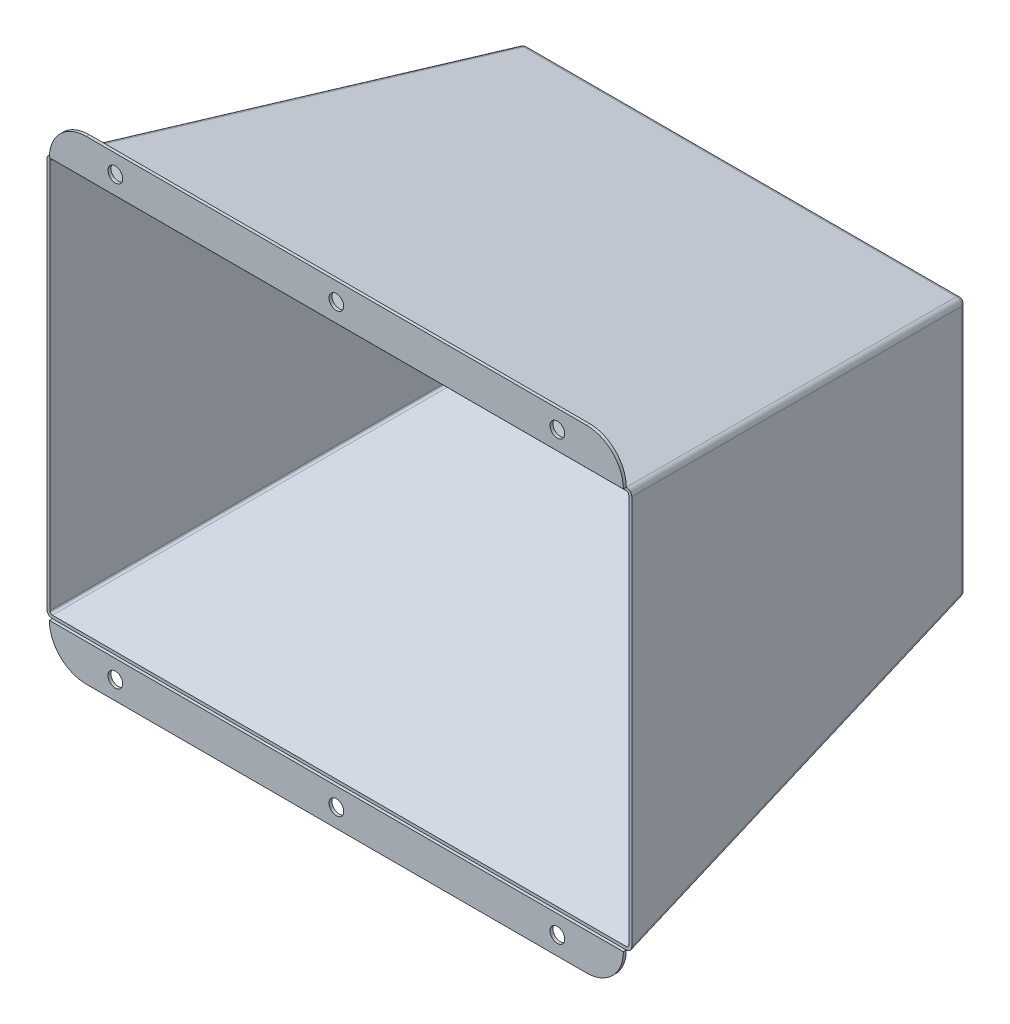
SolidWorks part; units mm, degrees
ref_plane "Alzado" through (0, 0, 0) normal (0, 0, 1) x (1, 0, 0)
ref_plane "Planta" through (0, 0, 0) normal (0, 1, 0) x (1, 0, 0)
ref_plane "Vista lateral" through (0, 0, 0) normal (1, 0, 0) x (0, 0, -1)
sketch "Croquis1" plane through (0, 0, 0) normal (0, 0, 1) x (1, 0, 0)
  line L1 (-120, 70) -> (120, 70)
  line L2 (-120, 70) -> (-120, -70)
  line L3 (-120, -70) -> (120, -70)
  line L4 (120, 70) -> (120, -70)
  line L5 (-120, 70) -> (120, -70) construction
  line L6 (-120, -70) -> (120, 70) construction
  point P0 (0, 0)
  dimension "D1" = 240
  dimension "D2" = 140
extrude "Saliente-Extruir1" add sketch "Croquis1" along normal blind 220 draft 10 draft outward yes
fillet "Redondeo1" radius 3 8 edges at (0, 70, 0) (-120, 0, 0) (0, -70, 0) (120, 0, 0) (139.396, -89.396, 110) (139.396, 89.396, 110) (-139.396, 89.396, 110) (-139.396, -89.396, 110)
shell "Vaciado1" thickness 1.6 removed face at (0, 0, 220)
sketch "Croquis2" plane through (0, 0, 220) normal (0, 0, 1) x (1, 0, 0)
  line L1 (-155.8375, 108.7919) -> (155.8375, 108.7919)
  line L2 (-155.8375, 108.7919) -> (-155.8375, 128.7919)
  line L3 (-155.8375, 128.7919) -> (155.8375, 128.7919)
  line L4 (155.8375, 108.7919) -> (155.8375, 128.7919)
  line L5 (-155.8375, -108.7919) -> (155.8375, -108.7919)
  line L6 (-155.8375, -108.7919) -> (-155.8375, -128.7919)
  line L7 (-155.8375, -128.7919) -> (155.8375, -128.7919)
  line L8 (155.8375, -108.7919) -> (155.8375, -128.7919)
  ellipse E0 centre (155.7457, 105.7457) end of major axis (153.5594, 103.5594) minor radius 3 (158.7919, 105.8375) -> (155.8375, 108.7919) ccw construction
  dimension "D1" = 20
  dimension "D2" = 20
extrude "Saliente-Extruir2" add sketch "Croquis2" along normal blind 1.6 separate body
fillet "Redondeo2" radius 20 2 edges at (-155.8375, 128.7919, 220.8) (155.8375, 128.7919, 220.8)
fillet "Redondeo3" radius 20 2 edges at (-155.8375, -128.7919, 220.8) (155.8375, -128.7919, 220.8)
sketch "Croquis3" plane through (0, 0, 221.6) normal (0, 0, 1) x (1, 0, 0)
  line L0 (-175.0203, 118.7919) -> (173.2976, 118.7919) construction
  line L2 (-155.8375, 108.7919) -> (155.8375, 108.7919) construction
  line L4 (0, 128.7919) -> (0, -128.7919) construction
  line L5 (135.8375, 128.7919) -> (-135.8375, 128.7919) construction
  line L6 (-135.8375, -128.7919) -> (135.8375, -128.7919) construction
  line L7 (0, 0) -> (208.2339, 0) construction
  circle A0 centre (0, 118.7919) radius 4
  circle A1 centre (120, 118.7919) radius 4
  circle A2 centre (-120, 118.7919) radius 4
  circle A3 centre (120, -118.7919) radius 4
  circle A4 centre (0, -118.7919) radius 4
  circle A5 centre (-120, -118.7919) radius 4
  dimension "D2" = 8
  dimension "D3" = 8
  dimension "D4" = 120
  dimension "D1" = 10
extrude "Cortar-Extruir1" cut sketch "Croquis3" against normal through all
sketch "Croquis4" plane through (0, 0, 0) normal (0, 0, -1) x (-1, 0, 0)
  line L0 (0, 0) -> (117.4827, 0) construction
  line L1 (117.4827, -67.4827) -> (117.4827, 67.4827) construction
  circle A0 centre (0, 0) radius 9
  circle A1 centre (50, 0) radius 3.25
  circle A2 centre (35.3553, -35.3553) radius 3.25
  circle A3 centre (0, -50) radius 3.25
  circle A4 centre (-35.3553, -35.3553) radius 3.25
  circle A5 centre (-50, 0) radius 3.25
  circle A6 centre (-35.3553, 35.3553) radius 3.25
  circle A7 centre (0, 50) radius 3.25
  circle A8 centre (35.3553, 35.3553) radius 3.25
  point P25 (0, 0)
  dimension "D1" = 18
  dimension "D2" = 50
  dimension "D3" = 6.5
  dimension "D4" = 8
extrude "Cortar-Extruir2" cut sketch "Croquis4" against normal through all
